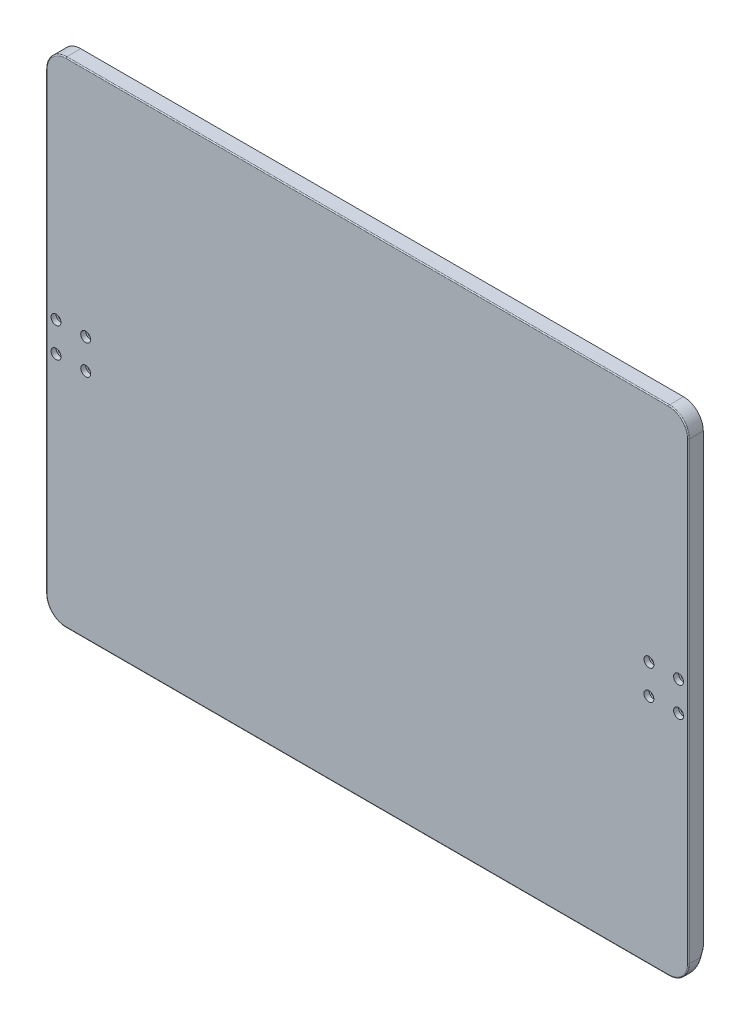
SolidWorks part; units mm, degrees
material "Beech"
ref_plane "Front Plane" through (0, 0, 0) normal (0, 0, 1) x (1, 0, 0)
ref_plane "Top Plane" through (0, 0, 0) normal (0, 1, 0) x (1, 0, 0)
ref_plane "Right Plane" through (0, 0, 0) normal (1, 0, 0) x (0, 0, -1)
sketch "Sketch1" plane through (0, 0, 0) normal (0, 0, 1) x (1, 0, 0)
  line L1 (0, 0) -> (650, 0)
  line L2 (0, 0) -> (0, 500)
  line L3 (0, 500) -> (650, 500)
  line L4 (650, 0) -> (650, 500)
  dimension "D1" = 500
  dimension "D2" = 650
extrude "base" add sketch "Sketch1" along normal blind 15
hole_wizard "counterbored M5 bolt holes" positions "Sketch2" profile "Sketch3" counterbore size "M5" standard "ANSI Metric" end condition through all
sketch "Sketch2" plane through (0, 0, 15) normal (0, 0, 1) x (1, 0, 0)
  line L1 (10, 265) -> (40, 265)
  line L2 (10, 265) -> (10, 235)
  line L3 (10, 235) -> (40, 235)
  line L4 (40, 265) -> (40, 235)
  line L5 (10, 250) -> (0, 250)
  line L6 (0, 500) -> (0, 0) construction
  point P1 (10, 265)
  point P2 (40, 235)
  point P41 (10, 235)
  point P42 (40, 265)
  dimension "D1" = 30
  dimension "D2" = 30
  dimension "D3" = 10
sketch "Sketch3" plane through (10, 265, 15) normal (1, 0, 0) x (0, -1, 0)
  line L0 (0, 0) -> (0, 15)
  line L1 (0, 15) -> (2.75, 15)
  line L3 (2.75, 15) -> (2.75, 5)
  line L4 (2.75, 5) -> (5, 5)
  line L5 (5, 5) -> (5, 0)
  line L7 (5, 0) -> (0, 0)
  line L11 (0, -6.35) -> (0, 107.95) construction
  dimension "Thru Hole Dia." = 5.5
  dimension "Thru Hole Depth" = 15
  dimension "C'Bore Dia." = 10
  dimension "C'Bore Depth" = 5
ref_plane "midplane in x" through (325, 0, 0) normal (-1, 0, 0) x (0, 0, 1)
mirror "mirror counterbored bolt holes" about plane through (325, 0, 0) normal (-1, 0, 0) of "counterbored M5 bolt holes"
fillet "round corners" radius 20 4 edges at (0, 500, 7.5) (650, 500, 7.5) (650, 0, 7.5) (0, 0, 7.5)
fillet "break top edge" radius 1 8 edges at (5.8579, 494.1421, 15) (325, 500, 15) (644.1421, 494.1421, 15) (650, 250, 15) (644.1421, 5.8579, 15) (325, 0, 15) (5.8579, 5.8579, 15) (0, 250, 15)
chamfer "Chamfer2" distance 25 angle 20 1 edges at (325, 0, 0) tangent propagation no first distance on face at (642.75, 265, 0)
fillet "Fillet3" radius 1 6 edges at (0, 22.5, 0.9099) (5.8579, 5.8579, 6.9672) (325, 0, 9.0993) (650, 22.5, 0.9099) (644.1421, 5.8579, 6.9672) (325, 25, 0)
equation "\"board_thickness\" = 12mm"
equation "\"way_width\"= 75mm"
equation "\"way_thickness\"= 50mm"
equation "\"radial_clearance\"= 0.1mm"
equation "\"slider_width\"= \"way_width\"-2* \"radial_clearance\""
equation "\"slider_thickness\" = \"way_thickness\" - 2 * \"radial_clearance\""
equation "\"column_width\"= \"way_width\" + 2 * \"board_thickness\""
equation "\"boxway_slot_width\" = 50mm"
equation "\"keeper_rail_width\" = (\"column_width\" - \"boxway_slot_width\")/2"
equation "\"slider_length\" = 125mm"
equation "\"nut_diameter\"= 22mm"
equation "\"nut_length\"= 15mm"
equation "\"leadscrew_diameter\"= 10mm"
equation "\"leadscrew_radial_clearance\"= 1mm"
equation "\"bearing_bolt_pattern_width\" = 35mm"
equation "\"bearing_bolt_pattern_height\" = 60mm"
equation "\"desktop_bolt_pattern_width\" = 30mm"
equation "\"desktop_bolt_pattern_height\" = 30mm"
equation "\"bearing_bolt_nut_counterbore_diameter\" = 12mm"
equation "\"bearing_bolt_nut_counterbore_depth\"= 10mm"
equation "\"desktop_depth\"= 500mm"
equation "\"desktop_width\"= 650mm"
equation "\"D1@Sketch1\"=\"desktop_depth\""
equation "\"D2@Sketch1\"=\"desktop_width\""
equation "\"desktop_thickness\"= 15mm"
equation "\"D1@base\" = \"desktop_thickness\""
equation "\"D1@Sketch2\"=\"desktop_bolt_pattern_height\""
equation "\"D2@Sketch2\"=\"desktop_bolt_pattern_width\""
